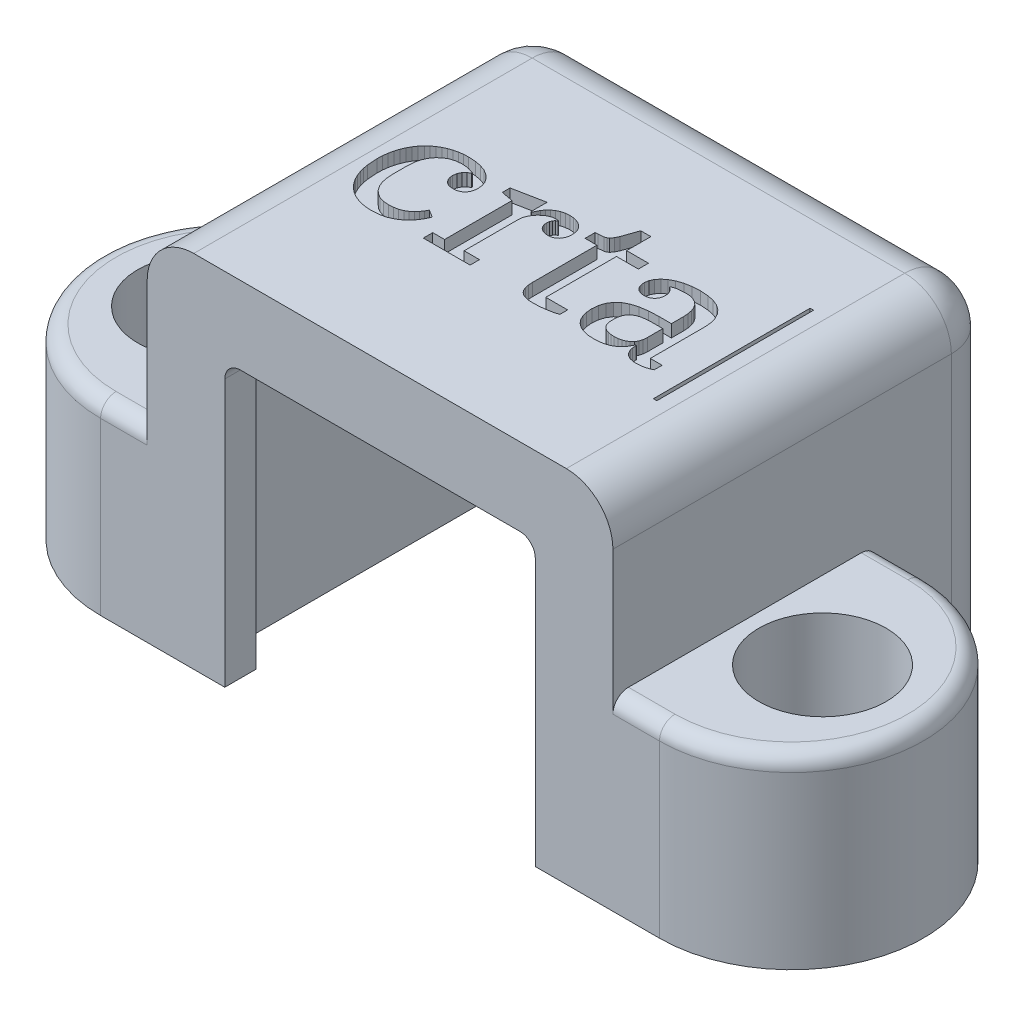
SolidWorks part; units mm, degrees
material "Custom Plastic"
ref_plane "Front Plane" through (0, 0, 0) normal (0, 0, 1) x (1, 0, 0)
ref_plane "Top Plane" through (0, 0, 0) normal (0, 1, 0) x (1, 0, 0)
ref_plane "Right Plane" through (0, 0, 0) normal (1, 0, 0) x (0, 0, -1)
sketch "Sketch1" plane through (0, 0, 0) normal (0, 0, 1) x (1, 0, 0)
  line L0 (0, -210.3757) -> (0, 10308.4069) construction
  line L1 (0, 0) -> (6, 0)
  line L2 (6, 0) -> (6, -10.1)
  line L3 (0, 1.5) -> (7.5, 1.5)
  line L4 (7.5, 1.5) -> (7.5, -10.1)
  line L5 (7.5, -10.1) -> (6, -10.1)
  line L6 (-7.5, -10.1) -> (-6, -10.1)
  line L7 (-7.5, 1.5) -> (-7.5, -10.1)
  line L8 (0, 1.5) -> (-7.5, 1.5)
  line L9 (-6, 0) -> (-6, -10.1)
  line L10 (0, 0) -> (-6, 0)
  dimension "D1" = 12
  dimension "D2" = 10.1
  dimension "D3" = 1.5
extrude "Boss-Extrude1" add sketch "Sketch1" along normal blind 12.4
sketch "Sketch3" plane through (0, -10.1, 0) normal (0, -1, 0) x (1, 0, 0)
  line L0 (0, -1000) -> (0, 49000) construction
  line L1 (7.5, 0) -> (-7.5, 0) construction
  line L2 (7.5, 3.9) -> (7.5, 12.4)
  line L3 (7.5, 12.4) -> (7.5, 0) construction
  line L4 (7.5, 3.9) -> (9, 3.9)
  line L5 (7.5, 12.4) -> (9, 12.4)
  line L6 (-7.5, 12.4) -> (-9, 12.4)
  line L7 (-7.5, 3.9) -> (-9, 3.9)
  line L8 (-7.5, 3.9) -> (-7.5, 12.4)
  arc A0 (9, 3.9) -> (9, 12.4) centre (9, 8.15) ccw
  arc A1 (-9, 3.9) -> (-9, 12.4) centre (-9, 8.15) cw
  point P5 (0, 0)
  point P10 (7.5, 8.15)
  point P22 (-7.5, 8.15)
  dimension "D1" = 8.5
  dimension "D2" = 1.5
extrude "Boss-Extrude2" add sketch "Sketch3" against normal blind 6
sketch "Sketch4" plane through (0, -10.1, 0) normal (0, -1, 0) x (1, 0, 0)
  line L1 (0, -1000) -> (0, 49000) construction
  circle A0 centre (-10, 8.15) radius 2.05
  circle A2 centre (10, 8.15) radius 2.05
  arc A3 (-9, 12.4) -> (-9, 3.9) centre (-9, 8.15) ccw construction
  point P3 (-9, 8.15)
  dimension "D1" = 4.1
  dimension "D2" = 1
extrude "Cut-Extrude1" cut sketch "Sketch4" against normal up to surface (6 mm away) up to face at (9.3125, -4.1, 8.15)
fillet "Fillet1" radius 1.5 2 edges at (-7.5, 1.5, 6.2) (7.5, 1.5, 6.2)
fillet "Fillet2" radius 0.5 6 edges at (8.25, -4.1, 3.9) (8.25, -4.1, 12.4) (13.25, -4.1, 8.15) (-8.25, -4.1, 12.4) (-13.25, -4.1, 8.15) (-8.25, -4.1, 3.9)
fillet "Fillet3" radius 1 2 edges at (-6, 0, 6.2) (6, 0, 6.2)
sketch "Sketch6" plane through (0, 0, 12.4) normal (0, 0, -1) x (-1, 0, 0)
  line L0 (6, -10.1) -> (6, -1) construction
  line L1 (5, 0) -> (-5, 0) construction
  line L2 (-6, -1) -> (-6, -10.1) construction
  line L3 (6, -10.1) -> (6, -1)
  line L4 (5, 0) -> (-5, 0)
  line L5 (-6, -1) -> (-6, -10.1)
  line L6 (5, -10.1) -> (5, -1)
  line L7 (5, -1) -> (-5, -1)
  line L8 (-5, -1) -> (-5, -10.1)
  line L9 (-5, -10.1) -> (-6, -10.1)
  line L10 (5, -10.1) -> (6, -10.1)
  arc A0 (6, -1) -> (5, 0) centre (5, -1) ccw construction
  arc A1 (-5, 0) -> (-6, -1) centre (-5, -1) ccw construction
  arc A2 (6, -1) -> (5, 0) centre (5, -1) ccw
  arc A3 (-5, 0) -> (-6, -1) centre (-5, -1) ccw
  arc A4 (5, -1) -> (5, -1) centre (5, -1) ccw
  arc A5 (-5, -1) -> (-5, -1) centre (-5, -1) ccw
  dimension "D1" = 1
extrude "Boss-Extrude3" add sketch "Sketch6" along normal blind 1
fillet "Fillet4" radius 0.5 2 edges at (-5, -1, 11.9) (5, -1, 11.9)
ref_plane "Plane1" through (0, 0, 5.55) normal (0, 0, -1) x (-1, 0, 0)
sketch "Sketch7" plane through (0, 0, 5.55) normal (0, 0, -1) x (-1, 0, 0)
  line L0 (-6, -2) -> (-4, 0)
  line L1 (-6, -1) -> (-6, -10.1) construction
  line L2 (5, 0) -> (-5, 0) construction
  line L3 (5, 0) -> (-5, 0) construction
  line L4 (-6, -1) -> (-6, -10.1) construction
  line L5 (-4, 0) -> (-5, 0)
  line L6 (-6, -1) -> (-6, -2)
  line L7 (0, -1000) -> (0, 49000) construction
  line L8 (6, -1) -> (6, -2)
  line L9 (4, 0) -> (5, 0)
  line L10 (6, -2) -> (4, 0)
  arc A0 (-5, 0) -> (-6, -1) centre (-5, -1) ccw construction
  arc A1 (-5, 0) -> (-6, -1) centre (-5, -1) ccw
  arc A2 (5, 0) -> (6, -1) centre (5, -1) cw
  dimension "D1" = 45
  dimension "D2" = 2
extrude "Boss-Extrude4" add sketch "Sketch7" along normal blind 1 contours L5 A1 L6 L0 | A2 L9 L10 L8 region at (5.28, -0.72, 5.55) region at (-5.28, -0.72, 5.55)
fillet "Fillet5" radius 1.5 5 edges at (-7.5, -5.05, 0) (-7.0607, 1.0607, 0) (0, 1.5, 0) (7.0607, 1.0607, 0) (7.5, -5.05, 0)
sketch "Sketch8" plane through (0, 1.5, 0) normal (0, 1, 0) x (1, 0, 0)
  line B0 (-4.3206, -8.3419) -> (-4.4819, -8.3349)
  line B1 (-4.4819, -8.3349) -> (-4.6341, -8.3138)
  line B2 (-4.6341, -8.3138) -> (-4.7771, -8.2786)
  line B3 (-4.7771, -8.2786) -> (-4.911, -8.2294)
  line B4 (-4.911, -8.2294) -> (-5.0326, -8.1676)
  line B5 (-5.0326, -8.1676) -> (-5.1444, -8.0945)
  line B6 (-5.1444, -8.0945) -> (-5.2463, -8.0101)
  line B7 (-5.2463, -8.0101) -> (-5.3384, -7.9146)
  line B8 (-5.3384, -7.9146) -> (-5.4203, -7.8084)
  line B9 (-5.4203, -7.8084) -> (-5.4916, -7.6924)
  line B10 (-5.4916, -7.6924) -> (-5.5524, -7.5666)
  line B11 (-5.5524, -7.5666) -> (-5.6027, -7.431)
  line B12 (-5.6027, -7.431) -> (-5.6421, -7.2869)
  line B13 (-5.6421, -7.2869) -> (-5.6702, -7.1357)
  line B14 (-5.6702, -7.1357) -> (-5.6927, -6.8124)
  line B15 (-5.6927, -6.8124) -> (-5.686, -6.6374)
  line B16 (-5.686, -6.6374) -> (-5.666, -6.4722)
  line B17 (-5.666, -6.4722) -> (-5.6326, -6.3169)
  line B18 (-5.6326, -6.3169) -> (-5.5858, -6.1714)
  line B19 (-5.5858, -6.1714) -> (-5.5271, -6.0336)
  line B20 (-5.5271, -6.0336) -> (-5.4579, -5.9071)
  line B21 (-5.4579, -5.9071) -> (-5.3781, -5.7918)
  line B22 (-5.3781, -5.7918) -> (-5.2878, -5.6878)
  line B23 (-5.2878, -5.6878) -> (-5.188, -5.5954)
  line B24 (-5.188, -5.5954) -> (-5.0797, -5.5149)
  line B25 (-5.0797, -5.5149) -> (-4.9631, -5.4463)
  line B26 (-4.9631, -5.4463) -> (-4.8379, -5.3898)
  line B27 (-4.8379, -5.3898) -> (-4.703, -5.343)
  line B28 (-4.703, -5.343) -> (-4.5624, -5.3096)
  line B29 (-4.5624, -5.3096) -> (-4.4162, -5.2896)
  line B30 (-4.4162, -5.2896) -> (-4.2644, -5.2829)
  line B31 (-4.2644, -5.2829) -> (-4.0359, -5.2956)
  line B32 (-4.0359, -5.2956) -> (-3.8342, -5.3335)
  line B33 (-3.8342, -5.3335) -> (-3.6592, -5.3968)
  line B34 (-3.6592, -5.3968) -> (-3.5109, -5.4853)
  line B35 (-3.5109, -5.4853) -> (-3.3903, -5.5936)
  line B36 (-3.3903, -5.5936) -> (-3.3042, -5.7159)
  line B37 (-3.3042, -5.7159) -> (-3.2526, -5.8523)
  line B38 (-3.2526, -5.8523) -> (-3.2353, -6.0027)
  line B39 (-3.2353, -6.0027) -> (-3.242, -6.0958)
  line B40 (-3.242, -6.0958) -> (-3.2621, -6.1784)
  line B41 (-3.2621, -6.1784) -> (-3.2954, -6.2505)
  line B42 (-3.2954, -6.2505) -> (-3.3422, -6.312)
  line B43 (-3.3422, -6.312) -> (-3.4002, -6.3587)
  line B44 (-3.4002, -6.3587) -> (-3.4673, -6.3921)
  line B45 (-3.4673, -6.3921) -> (-3.5436, -6.4121)
  line B46 (-3.5436, -6.4121) -> (-3.629, -6.4188)
  line B47 (-3.629, -6.4188) -> (-3.7161, -6.4125)
  line B48 (-3.7161, -6.4125) -> (-3.792, -6.3935)
  line B49 (-3.792, -6.3935) -> (-3.8567, -6.3619)
  line B50 (-3.8567, -6.3619) -> (-3.9101, -6.3176)
  line B51 (-3.9101, -6.3176) -> (-3.9519, -6.261)
  line B52 (-3.9519, -6.261) -> (-3.9818, -6.1981)
  line B53 (-3.9818, -6.1981) -> (-3.9997, -6.1289)
  line B54 (-3.9997, -6.1289) -> (-4.0057, -6.0533)
  line B55 (-4.0057, -6.0533) -> (-3.9889, -5.9324)
  line B56 (-3.9889, -5.9324) -> (-3.9382, -5.8284)
  line B57 (-3.9382, -5.8284) -> (-3.8609, -5.7454)
  line B58 (-3.8609, -5.7454) -> (-3.7639, -5.6878)
  line B59 (-3.7639, -5.6878) -> (-3.7639, -5.6597)
  line B60 (-3.7639, -5.6597) -> (-3.9326, -5.6091)
  line B61 (-3.9326, -5.6091) -> (-4.0465, -5.588)
  line B62 (-4.0465, -5.588) -> (-4.1857, -5.5809)
  line B63 (-4.1857, -5.5809) -> (-4.3628, -5.5978)
  line B64 (-4.3628, -5.5978) -> (-4.5231, -5.6484)
  line B65 (-4.5231, -5.6484) -> (-4.6636, -5.73)
  line B66 (-4.6636, -5.73) -> (-4.7817, -5.8396)
  line B67 (-4.7817, -5.8396) -> (-4.8773, -5.9703)
  line B68 (-4.8773, -5.9703) -> (-4.9504, -6.1264)
  line B69 (-4.9504, -6.1264) -> (-4.9926, -6.3049)
  line B70 (-4.9926, -6.3049) -> (-5.0066, -6.5031)
  line B71 (-5.0066, -6.5031) -> (-5.0066, -6.9924)
  line B72 (-5.0066, -6.9924) -> (-4.9936, -7.1923)
  line B73 (-4.9936, -7.1923) -> (-4.9546, -7.3705)
  line B74 (-4.9546, -7.3705) -> (-4.8896, -7.5269)
  line B75 (-4.8896, -7.5269) -> (-4.7986, -7.6615)
  line B76 (-4.7986, -7.6615) -> (-4.6851, -7.7673)
  line B77 (-4.6851, -7.7673) -> (-4.5526, -7.8429)
  line B78 (-4.5526, -7.8429) -> (-4.4011, -7.8882)
  line B79 (-4.4011, -7.8882) -> (-4.2306, -7.9033)
  line B80 (-4.2306, -7.9033) -> (-4.0714, -7.8942)
  line B81 (-4.0714, -7.8942) -> (-3.9312, -7.8668)
  line B82 (-3.9312, -7.8668) -> (-3.81, -7.8211)
  line B83 (-3.81, -7.8211) -> (-3.7077, -7.7571)
  line B84 (-3.7077, -7.7571) -> (-3.6177, -7.6798)
  line B85 (-3.6177, -7.6798) -> (-3.539, -7.594)
  line B86 (-3.539, -7.594) -> (-3.4715, -7.4998)
  line B87 (-3.4715, -7.4998) -> (-3.4153, -7.3972)
  line B88 (-3.4153, -7.3972) -> (-3.1735, -7.5434)
  line B89 (-3.1735, -7.5434) -> (-3.2354, -7.6882)
  line B90 (-3.2354, -7.6882) -> (-3.3197, -7.8302)
  line B91 (-3.3197, -7.8302) -> (-3.4265, -7.9652)
  line B92 (-3.4265, -7.9652) -> (-3.5559, -8.0889)
  line B93 (-3.5559, -8.0889) -> (-3.7091, -8.1915)
  line B94 (-3.7091, -8.1915) -> (-3.8876, -8.2744)
  line B95 (-3.8876, -8.2744) -> (-4.0915, -8.325)
  line B96 (-4.0915, -8.325) -> (-4.3206, -8.3419)
  line B97 (-2.7326, -7.9708) -> (-2.3502, -7.9708)
  line B98 (-2.3502, -7.9708) -> (-2.3502, -5.8002)
  line B99 (-2.3502, -5.8002) -> (-2.7326, -5.7271)
  line B100 (-2.7326, -5.7271) -> (-2.7326, -5.4797)
  line B101 (-2.7326, -5.4797) -> (-1.7373, -5.2829)
  line B102 (-1.7373, -5.2829) -> (-1.7373, -5.8059)
  line B103 (-1.7373, -5.8059) -> (-1.7091, -5.8059)
  line B104 (-1.7091, -5.8059) -> (-1.6136, -5.6147)
  line B105 (-1.6136, -5.6147) -> (-1.5461, -5.5247)
  line B106 (-1.5461, -5.5247) -> (-1.4674, -5.446)
  line B107 (-1.4674, -5.446) -> (-1.3718, -5.3799)
  line B108 (-1.3718, -5.3799) -> (-1.2649, -5.3279)
  line B109 (-1.2649, -5.3279) -> (-1.1398, -5.2942)
  line B110 (-1.1398, -5.2942) -> (-1.0006, -5.2829)
  line B111 (-1.0006, -5.2829) -> (-0.878, -5.291)
  line B112 (-0.878, -5.291) -> (-0.7687, -5.3153)
  line B113 (-0.7687, -5.3153) -> (-0.6727, -5.3557)
  line B114 (-0.6727, -5.3557) -> (-0.5901, -5.4122)
  line B115 (-0.5901, -5.4122) -> (-0.5213, -5.4839)
  line B116 (-0.5213, -5.4839) -> (-0.4721, -5.5697)
  line B117 (-0.4721, -5.5697) -> (-0.4425, -5.6695)
  line B118 (-0.4425, -5.6695) -> (-0.4327, -5.7834)
  line B119 (-0.4327, -5.7834) -> (-0.439, -5.8741)
  line B120 (-0.439, -5.8741) -> (-0.458, -5.9549)
  line B121 (-0.458, -5.9549) -> (-0.4896, -6.0259)
  line B122 (-0.4896, -6.0259) -> (-0.5339, -6.087)
  line B123 (-0.5339, -6.087) -> (-0.5863, -6.1338)
  line B124 (-0.5863, -6.1338) -> (-0.6478, -6.1672)
  line B125 (-0.6478, -6.1672) -> (-0.7184, -6.1872)
  line B126 (-0.7184, -6.1872) -> (-0.7982, -6.1939)
  line B127 (-0.7982, -6.1939) -> (-0.8808, -6.1882)
  line B128 (-0.8808, -6.1882) -> (-0.9542, -6.1714)
  line B129 (-0.9542, -6.1714) -> (-1.0186, -6.1433)
  line B130 (-1.0186, -6.1433) -> (-1.0737, -6.1039)
  line B131 (-1.0737, -6.1039) -> (-1.1155, -6.0533)
  line B132 (-1.1155, -6.0533) -> (-1.1454, -5.9971)
  line B133 (-1.1454, -5.9971) -> (-1.1633, -5.9352)
  line B134 (-1.1633, -5.9352) -> (-1.1693, -5.8677)
  line B135 (-1.1693, -5.8677) -> (-1.1595, -5.7806)
  line B136 (-1.1595, -5.7806) -> (-1.13, -5.7103)
  line B137 (-1.13, -5.7103) -> (-1.0864, -5.6569)
  line B138 (-1.0864, -5.6569) -> (-1.0344, -5.6316)
  line B139 (-1.0344, -5.6316) -> (-1.0344, -5.6147)
  line B140 (-1.0344, -5.6147) -> (-1.0737, -5.6091)
  line B141 (-1.0737, -5.6091) -> (-1.1412, -5.6034)
  line B142 (-1.1412, -5.6034) -> (-1.248, -5.6175)
  line B143 (-1.248, -5.6175) -> (-1.3549, -5.6597)
  line B144 (-1.3549, -5.6597) -> (-1.4519, -5.7243)
  line B145 (-1.4519, -5.7243) -> (-1.5405, -5.8059)
  line B146 (-1.5405, -5.8059) -> (-1.6121, -5.8972)
  line B147 (-1.6121, -5.8972) -> (-1.6698, -6.0027)
  line B148 (-1.6698, -6.0027) -> (-1.7077, -6.1095)
  line B149 (-1.7077, -6.1095) -> (-1.7204, -6.2164)
  line B150 (-1.7204, -6.2164) -> (-1.7204, -7.9708)
  line B151 (-1.7204, -7.9708) -> (-1.2256, -7.9708)
  line B152 (-1.2256, -7.9708) -> (-1.2256, -8.2744)
  line B153 (-1.2256, -8.2744) -> (-2.7326, -8.2744)
  line B154 (-2.7326, -8.2744) -> (-2.7326, -7.9708)
  line B155 (0.8414, -8.3194) -> (0.6931, -8.311)
  line B156 (0.6931, -8.311) -> (0.5687, -8.2857)
  line B157 (0.5687, -8.2857) -> (0.4682, -8.2435)
  line B158 (0.4682, -8.2435) -> (0.3916, -8.1845)
  line B159 (0.3916, -8.1845) -> (0.335, -8.1071)
  line B160 (0.335, -8.1071) -> (0.2946, -8.0101)
  line B161 (0.2946, -8.0101) -> (0.2703, -7.8935)
  line B162 (0.2703, -7.8935) -> (0.2623, -7.7571)
  line B163 (0.2623, -7.7571) -> (0.2623, -5.6765)
  line B164 (0.2623, -5.6765) -> (-0.1201, -5.6765)
  line B165 (-0.1201, -5.6765) -> (-0.1201, -5.3504)
  line B166 (-0.1201, -5.3504) -> (-0.0245, -5.3504)
  line B167 (-0.0245, -5.3504) -> (0.1512, -5.3321)
  line B168 (0.1512, -5.3321) -> (0.2148, -5.3093)
  line B169 (0.2148, -5.3093) -> (0.2623, -5.2773)
  line B170 (0.2623, -5.2773) -> (0.3339, -5.1873)
  line B171 (0.3339, -5.1873) -> (0.3916, -5.0636)
  line B172 (0.3916, -5.0636) -> (0.5659, -4.5688)
  line B173 (0.5659, -4.5688) -> (0.892, -4.5688)
  line B174 (0.892, -4.5688) -> (0.892, -5.3504)
  line B175 (0.892, -5.3504) -> (1.5949, -5.3504)
  line B176 (1.5949, -5.3504) -> (1.5949, -5.6765)
  line B177 (1.5949, -5.6765) -> (0.892, -5.6765)
  line B178 (0.892, -5.6765) -> (0.892, -7.9539)
  line B179 (0.892, -7.9539) -> (1.5949, -7.9539)
  line B180 (1.5949, -7.9539) -> (1.5949, -8.2013)
  line B181 (1.5949, -8.2013) -> (1.4698, -8.2435)
  line B182 (1.4698, -8.2435) -> (1.2857, -8.2801)
  line B183 (1.2857, -8.2801) -> (1.0706, -8.3096)
  line B184 (1.0706, -8.3096) -> (0.8414, -8.3194)
  line B185 (2.8339, -8.3419) -> (2.6279, -8.3286)
  line B186 (2.6279, -8.3286) -> (2.4487, -8.2885)
  line B187 (2.4487, -8.2885) -> (2.2962, -8.2217)
  line B188 (2.2962, -8.2217) -> (2.1703, -8.1282)
  line B189 (2.1703, -8.1282) -> (2.0744, -8.0087)
  line B190 (2.0744, -8.0087) -> (2.0059, -7.8696)
  line B191 (2.0059, -7.8696) -> (1.9647, -7.7107)
  line B192 (1.9647, -7.7107) -> (1.951, -7.5322)
  line B193 (1.951, -7.5322) -> (1.97, -7.3315)
  line B194 (1.97, -7.3315) -> (2.027, -7.1568)
  line B195 (2.027, -7.1568) -> (2.1218, -7.0082)
  line B196 (2.1218, -7.0082) -> (2.2547, -6.8855)
  line B197 (2.2547, -6.8855) -> (2.4304, -6.7896)
  line B198 (2.4304, -6.7896) -> (2.6539, -6.721)
  line B199 (2.6539, -6.721) -> (2.9253, -6.6799)
  line B200 (2.9253, -6.6799) -> (3.2444, -6.6662)
  line B201 (3.2444, -6.6662) -> (3.6492, -6.6662)
  line B202 (3.6492, -6.6662) -> (3.6492, -6.2838)
  line B203 (3.6492, -6.2838) -> (3.6397, -6.1225)
  line B204 (3.6397, -6.1225) -> (3.6113, -5.9816)
  line B205 (3.6113, -5.9816) -> (3.5638, -5.861)
  line B206 (3.5638, -5.861) -> (3.4974, -5.7609)
  line B207 (3.4974, -5.7609) -> (3.4106, -5.6822)
  line B208 (3.4106, -5.6822) -> (3.302, -5.6259)
  line B209 (3.302, -5.6259) -> (3.1716, -5.5922)
  line B210 (3.1716, -5.5922) -> (3.0194, -5.5809)
  line B211 (3.0194, -5.5809) -> (2.7776, -5.6006)
  line B212 (2.7776, -5.6006) -> (2.6821, -5.6252)
  line B213 (2.6821, -5.6252) -> (2.6033, -5.6597)
  line B214 (2.6033, -5.6597) -> (2.6033, -5.6822)
  line B215 (2.6033, -5.6822) -> (2.6624, -5.7215)
  line B216 (2.6624, -5.7215) -> (2.7158, -5.7834)
  line B217 (2.7158, -5.7834) -> (2.758, -5.8649)
  line B218 (2.758, -5.8649) -> (2.772, -5.9746)
  line B219 (2.772, -5.9746) -> (2.766, -6.0494)
  line B220 (2.766, -6.0494) -> (2.7481, -6.1166)
  line B221 (2.7481, -6.1166) -> (2.7182, -6.1759)
  line B222 (2.7182, -6.1759) -> (2.6764, -6.2276)
  line B223 (2.6764, -6.2276) -> (2.6262, -6.2694)
  line B224 (2.6262, -6.2694) -> (2.5654, -6.2993)
  line B225 (2.5654, -6.2993) -> (2.494, -6.3172)
  line B226 (2.494, -6.3172) -> (2.4121, -6.3232)
  line B227 (2.4121, -6.3232) -> (2.3419, -6.3172)
  line B228 (2.3419, -6.3172) -> (2.2772, -6.2993)
  line B229 (2.2772, -6.2993) -> (2.2181, -6.2694)
  line B230 (2.2181, -6.2694) -> (2.1647, -6.2276)
  line B231 (2.1647, -6.2276) -> (2.1229, -6.1728)
  line B232 (2.1229, -6.1728) -> (2.093, -6.1095)
  line B233 (2.093, -6.1095) -> (2.0751, -6.0378)
  line B234 (2.0751, -6.0378) -> (2.0691, -5.9577)
  line B235 (2.0691, -5.9577) -> (2.0874, -5.8312)
  line B236 (2.0874, -5.8312) -> (2.1422, -5.7103)
  line B237 (2.1422, -5.7103) -> (2.2378, -5.5936)
  line B238 (2.2378, -5.5936) -> (2.3672, -5.491)
  line B239 (2.3672, -5.491) -> (2.5288, -5.4052)
  line B240 (2.5288, -5.4052) -> (2.7214, -5.3391)
  line B241 (2.7214, -5.3391) -> (2.9506, -5.297)
  line B242 (2.9506, -5.297) -> (3.2106, -5.2829)
  line B243 (3.2106, -5.2829) -> (3.4588, -5.2984)
  line B244 (3.4588, -5.2984) -> (3.6745, -5.3448)
  line B245 (3.6745, -5.3448) -> (3.858, -5.4221)
  line B246 (3.858, -5.4221) -> (4.0091, -5.5303)
  line B247 (4.0091, -5.5303) -> (4.1272, -5.6663)
  line B248 (4.1272, -5.6663) -> (4.2116, -5.8269)
  line B249 (4.2116, -5.8269) -> (4.2622, -6.0122)
  line B250 (4.2622, -6.0122) -> (4.279, -6.222)
  line B251 (4.279, -6.222) -> (4.279, -7.9764)
  line B252 (4.279, -7.9764) -> (4.6614, -7.9764)
  line B253 (4.6614, -7.9764) -> (4.6614, -8.2294)
  line B254 (4.6614, -8.2294) -> (4.5714, -8.2716)
  line B255 (4.5714, -8.2716) -> (4.459, -8.3082)
  line B256 (4.459, -8.3082) -> (4.331, -8.3335)
  line B257 (4.331, -8.3335) -> (4.1947, -8.3419)
  line B258 (4.1947, -8.3419) -> (4.0738, -8.3338)
  line B259 (4.0738, -8.3338) -> (3.9698, -8.3096)
  line B260 (3.9698, -8.3096) -> (3.8826, -8.2692)
  line B261 (3.8826, -8.2692) -> (3.8123, -8.2126)
  line B262 (3.8123, -8.2126) -> (3.7606, -8.1405)
  line B263 (3.7606, -8.1405) -> (3.7237, -8.0593)
  line B264 (3.7237, -8.0593) -> (3.7016, -7.969)
  line B265 (3.7016, -7.969) -> (3.6942, -7.8696)
  line B266 (3.6942, -7.8696) -> (3.6942, -7.8414)
  line B267 (3.6942, -7.8414) -> (3.6661, -7.8414)
  line B268 (3.6661, -7.8414) -> (3.5649, -8.027)
  line B269 (3.5649, -8.027) -> (3.4932, -8.1085)
  line B270 (3.4932, -8.1085) -> (3.4018, -8.1845)
  line B271 (3.4018, -8.1845) -> (3.295, -8.2491)
  line B272 (3.295, -8.2491) -> (3.1656, -8.2969)
  line B273 (3.1656, -8.2969) -> (3.0124, -8.3307)
  line B274 (3.0124, -8.3307) -> (2.8339, -8.3419)
  line B275 (3.0813, -7.9483) -> (3.1994, -7.9409)
  line B276 (3.1994, -7.9409) -> (3.3062, -7.9188)
  line B277 (3.3062, -7.9188) -> (3.4018, -7.8819)
  line B278 (3.4018, -7.8819) -> (3.4862, -7.8302)
  line B279 (3.4862, -7.8302) -> (3.5575, -7.7617)
  line B280 (3.5575, -7.7617) -> (3.6085, -7.6742)
  line B281 (3.6085, -7.6742) -> (3.639, -7.5677)
  line B282 (3.639, -7.5677) -> (3.6492, -7.4422)
  line B283 (3.6492, -7.4422) -> (3.6492, -6.9417)
  line B284 (3.6492, -6.9417) -> (3.3118, -6.9417)
  line B285 (3.3118, -6.9417) -> (3.1273, -6.9498)
  line B286 (3.1273, -6.9498) -> (2.9731, -6.9741)
  line B287 (2.9731, -6.9741) -> (2.849, -7.0145)
  line B288 (2.849, -7.0145) -> (2.7552, -7.0711)
  line B289 (2.7552, -7.0711) -> (2.6863, -7.1428)
  line B290 (2.6863, -7.1428) -> (2.6371, -7.2285)
  line B291 (2.6371, -7.2285) -> (2.6075, -7.3283)
  line B292 (2.6075, -7.3283) -> (2.5977, -7.4422)
  line B293 (2.5977, -7.4422) -> (2.5977, -7.549)
  line B294 (2.5977, -7.549) -> (2.6058, -7.6439)
  line B295 (2.6058, -7.6439) -> (2.63, -7.7262)
  line B296 (2.63, -7.7262) -> (2.6705, -7.7958)
  line B297 (2.6705, -7.7958) -> (2.727, -7.8527)
  line B298 (2.727, -7.8527) -> (2.7977, -7.8945)
  line B299 (2.7977, -7.8945) -> (2.8803, -7.9244)
  line B300 (2.8803, -7.9244) -> (2.9748, -7.9423)
  line B301 (2.9748, -7.9423) -> (3.0813, -7.9483)
  line B302 (5.4528, -4.0008) -> (5.5652, -4.0008)
  line B303 (5.5652, -4.0008) -> (5.5652, -9.0504)
  line B304 (5.5652, -9.0504) -> (5.4528, -9.0504)
  line B305 (5.4528, -9.0504) -> (5.4528, -4.0008)
sketch_block_instance "Block1-1"
sketch_block "Block1"
extrude "Cut-Extrude2" cut sketch "Sketch8" against normal blind 0.4
equation "\"Hole_Diameter\"= 4.1mm"
equation "\"Hole_Depth\"= 6mm"
equation "\"D1@Sketch4\"=\"Hole_Diameter\""
equation "\"D1@Boss-Extrude2\"=\"Hole_Depth\""
